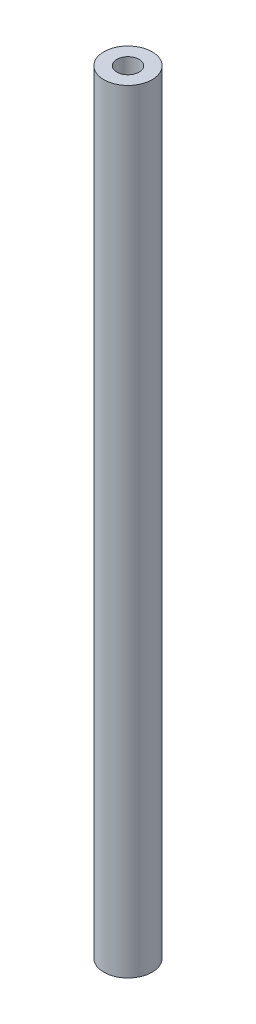
SolidWorks part; units mm, degrees
material "1060 Alloy"
ref_plane "Front Plane" through (0, 0, 0) normal (0, 0, 1) x (1, 0, 0)
ref_plane "Top Plane" through (0, 0, 0) normal (0, 1, 0) x (1, 0, 0)
ref_plane "Right Plane" through (0, 0, 0) normal (1, 0, 0) x (0, 0, -1)
sketch "Sketch1" plane through (0, 0, 0) normal (0, 1, 0) x (1, 0, 0)
  circle A0 centre (0, 0) radius 6.35
  dimension "D1" = 12.7
extrude "Boss-Extrude1" add sketch "Sketch1" along normal blind 203.2
sketch "Sketch2" plane through (0, 203.2, 0) normal (0, 1, 0) x (1, 0, 0)
  circle A0 centre (0, 0) radius 2.921
  dimension "D1" = 5.842
extrude "Cut-Extrude1" cut sketch "Sketch2" against normal blind 12.7
sketch "Sketch3" plane through (0, 0, 0) normal (1, 0, 0) x (0, 0, -1)
  line L0 (6.35, 203.2) -> (-6.35, 203.2) construction
  circle A0 centre (0, 196.85) radius 1.65
  dimension "D2" = 3.3
  dimension "D1" = 6.35
extrude "Cut-Extrude2" cut sketch "Sketch3" against normal through all
ref_axis "Axis1" through (-6.35, 196.85, 0) along (1, 0, 0)
ref_plane "Plane1" through (-6.35, 0, 0) normal (-1, 0, 0) x (0, 0, 1)
thread "Thread1" pitch 0.7 method cut profile "Thread Profile1" start angle 0, offset 1, length 0, pitch 0.7, diameter 3.3
ref_plane "Plane2" through (-7.35, 196.85, -1.65) normal (0, -1, 0) x (0, 0, -1)
sketch "Thread Profile1" plane through (-7.35, 196.85, -1.65) normal (0, -1, 0) x (0, 0, -1)
  line L0 (0, 0) -> (0, 0.7) construction
  line L1 (0, 0) -> (0.3789, 0.2187)
  line L2 (0.3789, 0.2187) -> (0.3789, 0.3062)
  line L3 (0.3789, 0.3062) -> (0, 0.525)
  line L4 (0.3789, 0.2625) -> (0, 0.2625) construction
  line L11 (0, 0) -> (0, 0.525)
  point P2 (0, 0)
  dimension "Pitch" = 0.7
  dimension "Profile_Angle" = 60
  dimension "Profile_Land" = 0.0875
  dimension "Profile_Height" = 0.3789
sketch "Sketch7" plane through (0, 0, 0) normal (0, -1, 0) x (1, 0, 0)
  line L1 (-3.175, -3.175) -> (3.175, -3.175)
  line L2 (-3.175, -3.175) -> (-3.175, 3.175)
  line L3 (-3.175, 3.175) -> (3.175, 3.175)
  line L4 (3.175, -3.175) -> (3.175, 3.175)
  line L5 (-3.175, -3.175) -> (3.175, 3.175) construction
  line L6 (-3.175, 3.175) -> (3.175, -3.175) construction
  point P0 (0, 0)
  dimension "D1" = 6.35
extrude "Cut-Extrude3" cut sketch "Sketch7" against normal blind 25.4
